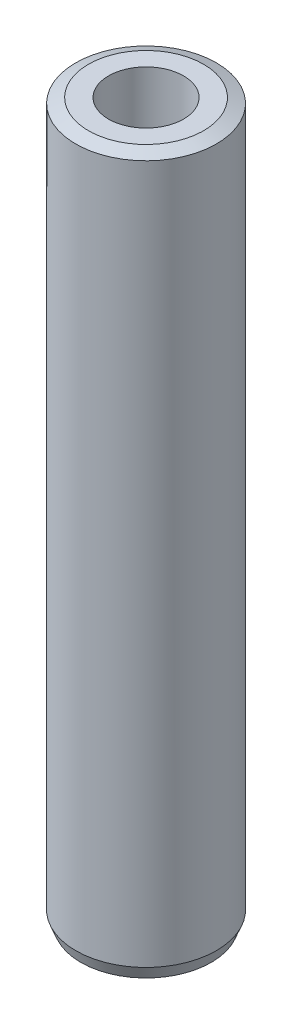
SolidWorks part; units mm, degrees
ref_plane "Front Plane" through (0, 0, 0) normal (0, 0, 1) x (1, 0, 0)
ref_plane "Top Plane" through (0, 0, 0) normal (0, 1, 0) x (1, 0, 0)
ref_plane "Right Plane" through (0, 0, 0) normal (1, 0, 0) x (0, 0, -1)
sketch "Sketch1" plane through (0, 0, 0) normal (0, 1, 0) x (1, 0, 0)
  circle A0 centre (0, 0) radius 12.5
  dimension "SHAFT_OD" = 25
extrude "Boss-Extrude1" add sketch "Sketch1" along normal blind 127.3128
sketch "Sketch2" plane through (0, 0, 0) normal (0, 1, 0) x (1, 0, 0)
  circle A0 centre (0, 0) radius 6.6652
  dimension "BORE_D" = 13.3303
extrude "Cut-Extrude1" cut sketch "Sketch2" along normal through all
chamfer "Chamfer1" distance 0.9056 angle 68.221 2 edges at (0, 127.3128, 12.5) (0, 0, 12.5) first distance on face at (0, 127.3128, 12.5) first distance on face at (0, 0, 6.6652)
